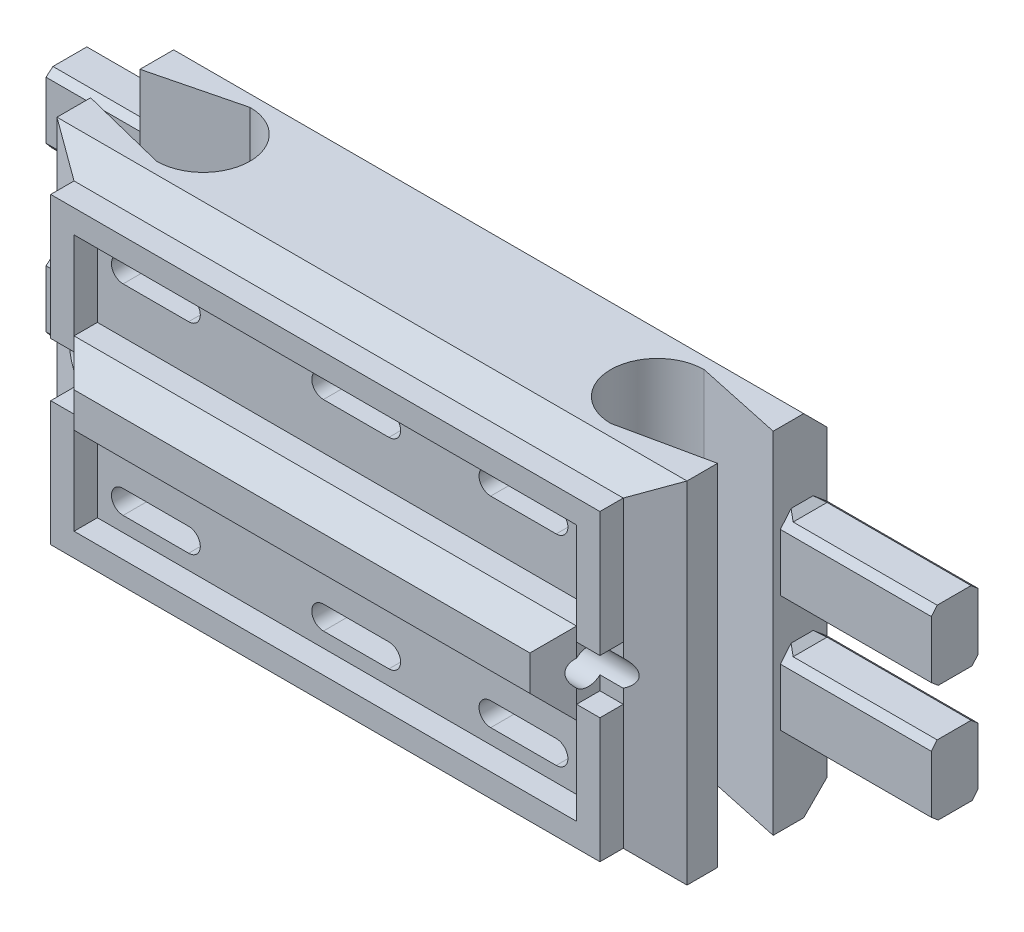
SolidWorks part; units mm, degrees
ref_plane "Front Plane" through (0, 0, 0) normal (0, 0, 1) x (1, 0, 0)
ref_plane "Top Plane" through (0, 0, 0) normal (0, 1, 0) x (1, 0, 0)
ref_plane "Right Plane" through (0, 0, 0) normal (1, 0, 0) x (0, 0, -1)
sketch "Base" plane through (0, 0, 0) normal (0, 0, 1) x (1, 0, 0)
  line L1 (0, 0) -> (27, 0)
  line L2 (0, 0) -> (0, 15)
  line L3 (0, 15) -> (27, 15)
  line L4 (27, 0) -> (27, 15)
  dimension "D1" = 27
  dimension "D2" = 15
extrude "Boss-Extrude1" add sketch "Base" along normal blind 7
chamfer "Chamfer4" distance 1 angle 45 2 edges at (13.5, 15, 7) (13.5, 0, 7)
chamfer "Chamfer5" distance 1 angle 60 2 edges at (0, 7.5, 7) (27, 7.5, 7)
chamfer "Chamfer6" distance 1 angle 45 2 edges at (13.5, 15, 0) (13.5, 0, 0)
sketch "Tendon extrude" plane through (0, 0, 0) normal (0, -1, 0) x (1, 0, 0)
  line L0 (13.5, 6) -> (13.5, -3.9632) construction
  line L1 (27, 6) -> (0, 6) construction
  line L2 (0, 3.5) -> (21.7648, 3.5) construction
  line L3 (0, 6) -> (0, 1) construction
  line L4 (3.77, 3.5) -> (-2.23, 3.5) construction
  line L5 (-2.23, 3) -> (-2.23, 4)
  line L6 (3.77, 5.5) -> (-2.23, 4)
  line L7 (-2.23, 3) -> (3.77, 1.5)
  line L10 (23.23, 3.5) -> (30.23, 3.5) construction
  line L11 (30.23, 3) -> (30.23, 4)
  line L12 (23.23, 5.5) -> (30.23, 4)
  line L13 (30.23, 3) -> (23.23, 1.5)
  circle A0 centre (3.77, 3.5) radius 2
  circle A1 centre (23.23, 3.5) radius 2
  dimension "D1" = 4
  dimension "D2" = 3.77
  dimension "D3" = 1
  dimension "D4" = 6
  dimension "D5" = 1
  dimension "D6" = 7
sketch "Sketch8" plane through (0, 0, 7) normal (0, 0, 1) x (1, 0, 0)
  line L0 (25.2679, 7.5) -> (1.7321, 7.5) construction
  line L1 (25.2679, 1) -> (25.2679, 14) construction
  line L2 (1.7321, 14) -> (1.7321, 1) construction
  line L3 (13.5, 1) -> (13.5, 14) construction
  line L4 (1.7321, 1) -> (25.2679, 1) construction
  line L5 (25.2679, 14) -> (1.7321, 14) construction
  line L6 (2.7321, 5.75) -> (2.7321, 9.25)
  line L7 (24.2679, 9.25) -> (2.7321, 9.25)
  line L8 (24.2679, 9.25) -> (24.2679, 5.75)
  line L9 (24.2679, 5.75) -> (2.7321, 5.75)
  point P17 (2.7321, 7.5)
  point P18 (24.2679, 7.5)
  dimension "D1" = 1.75
  dimension "D2" = 1
  dimension "D3" = 1
extrude "Boss-Extrude5" add sketch "Sketch8" along normal blind 2
sketch "Sketch9" plane through (24.2679, 0, 0) normal (1, 0, 0) x (0, 0, -1)
  line L0 (-9, 7.5) -> (-7, 7.5) construction
  line L1 (-9, 5.75) -> (-9, 9.25) construction
  line L2 (-7, 5.75) -> (-7, 9.25) construction
  circle A0 centre (-7.5, 7.5) radius 0.75
  dimension "D1" = 1.5
  dimension "D2" = 1.5
extrude "Cut-Extrude5" cut sketch "Sketch9" against normal blind 34.5 and the other way blind 4.2544
chamfer "Chamfer9" distance 1 angle 45 4 edges at (2.7321, 7.5, 9) (13.5, 9.25, 9) (24.2679, 7.5, 9) (13.5, 5.75, 9)
sketch "Sketch13" plane through (0, 0, 0) normal (0, 0, -1) x (-1, 0, 0)
  line L0 (0, 7.5) -> (-33.4926, 7.5) construction
  line L1 (0, 14) -> (0, 1) construction
  line L2 (-13.5, 1) -> (-13.5, 15.915) construction
  line L3 (-27, 1) -> (0, 1) construction
  line L4 (-1, 9.25) -> (-8.5, 9.25)
  line L5 (-18.5, 9.25) -> (-18.5, 5.75)
  line L6 (-1, 9.25) -> (-1, 5.75)
  line L7 (-1, 5.75) -> (-8.5, 5.75)
  line L8 (-8.5, 9.25) -> (-8.5, 5.75)
  line L9 (-26, 9.25) -> (-18.5, 9.25)
  line L10 (-26, 5.75) -> (-18.5, 5.75)
  line L11 (-26, 9.25) -> (-26, 5.75)
  point P13 (-8.5, 7.5)
  point P14 (-1, 7.5)
  dimension "D1" = 1.75
  dimension "D2" = 1
  dimension "D3" = 5
extrude "Boss-Extrude6" add sketch "Sketch13" along normal blind 2
chamfer "Chamfer10" distance 1 angle 45 8 edges at (18.5, 7.5, -2) (22.25, 5.75, -2) (26, 7.5, -2) (22.25, 9.25, -2) (4.75, 9.25, -2) (1, 7.5, -2) (4.75, 5.75, -2) (8.5, 7.5, -2)
sketch "Sketch14" plane through (1, 0, 0) normal (-1, 0, 0) x (0, 0, 1)
  line L0 (-1, 7.5) -> (0, 7.5) construction
  line L1 (-1, 9.25) -> (-1, 5.75) construction
  line L2 (0, 5.75) -> (0, 9.25) construction
  line L3 (-2, 6.75) -> (-2, 8.25) construction
  circle A0 centre (-0.5, 7.5) radius 0.75
  dimension "D1" = 1.5
  dimension "D2" = 1.5
extrude "Cut-Extrude6" cut sketch "Sketch14" against normal blind 30 and the other way blind 3
sketch "Sketch15" plane through (0, 0, 0) normal (0, 0, -1) x (-1, 0, 0)
  line L0 (-25, 6.75) -> (-19.5, 6.75) construction
  line L1 (-25, 3.25) -> (-24, 3.25)
  line L2 (-25, 3.25) -> (-25, 6.75)
  line L3 (-25, 6.75) -> (-24, 6.75)
  line L4 (-24, 3.25) -> (-24, 6.75)
  line L5 (-25, 8.25) -> (-25, 6.75) construction
  line L6 (-13.5, 1) -> (-13.5, 14) construction
  line L7 (-27, 1) -> (0, 1) construction
  line L8 (0, 14) -> (-27, 14) construction
  line L9 (-19.5, 8.25) -> (-25, 8.25) construction
  line L10 (-25, 8.25) -> (-24, 8.25)
  line L11 (-25, 8.25) -> (-25, 11.75)
  line L12 (-25, 11.75) -> (-24, 11.75)
  line L13 (-24, 8.25) -> (-24, 11.75)
  line L14 (-2, 3.25) -> (-3, 3.25)
  line L15 (-2, 3.25) -> (-2, 6.75)
  line L16 (-3, 3.25) -> (-3, 6.75)
  line L17 (-2, 6.75) -> (-3, 6.75)
  line L18 (-2, 8.25) -> (-3, 8.25)
  line L19 (-2, 11.75) -> (-3, 11.75)
  line L20 (-3, 8.25) -> (-3, 11.75)
  line L21 (-2, 8.25) -> (-2, 11.75)
  dimension "D1" = 0
  dimension "D2" = 3.5
  dimension "D3" = 1
  dimension "D4" = 0
  dimension "D5" = 0
extrude "Boss-Extrude7" add sketch "Sketch15" along normal blind 2
sketch "Sketch16" plane through (25, 0, 0) normal (1, 0, 0) x (0, 0, -1)
  line L0 (0.6, 5.15) -> (0.6, 4.35) construction
  line L1 (1.2, 5.15) -> (1.2, 4.35)
  line L2 (0, 5.15) -> (0, 4.35)
  line L3 (1, 5.75) -> (0, 5.75) construction
  line L5 (0.6, 9.85) -> (0.6, 10.65) construction
  line L6 (0, 9.85) -> (0, 10.65)
  line L7 (1.2, 9.85) -> (1.2, 10.65)
  line L9 (1, 9.25) -> (0, 9.25) construction
  line L10 (0, 5.75) -> (0, 3.25) construction
  arc A0 (1.2, 5.15) -> (0, 5.15) centre (0.6, 5.15) ccw
  arc A1 (0, 4.35) -> (1.2, 4.35) centre (0.6, 4.35) ccw
  arc A2 (0, 9.85) -> (1.2, 9.85) centre (0.6, 9.85) ccw
  arc A3 (1.2, 10.65) -> (0, 10.65) centre (0.6, 10.65) ccw
  point P2 (0.6, 4.75)
  point P13 (0.6, 10.25)
  point P20 (0.5, 9.25)
  dimension "D1" = 0.8
  dimension "D2" = 0.6
  dimension "D3" = 0.6
  dimension "D4" = 0
  dimension "D5" = 0.6
extrude "Cut-Extrude7" cut sketch "Sketch16" against normal blind 26
chamfer "Chamfer11" distance 0.3 angle 45 8 edges at (2, 5, -2) (3, 5, -2) (3, 10, -2) (2, 10, -2) (25, 10, -2) (24, 10, -2) (25, 5, -2) (24, 5, -2)
chamfer "Chamfer12" distance 0.75 angle 45 4 edges at (24.5, 3.25, -2) (24.5, 11.75, -2) (2.5, 11.75, -2) (2.5, 3.25, -2)
extrude "Cut-Extrude8" cut sketch "Tendon extrude" against normal up to surface (15 mm away)
sketch "Sketch18" plane through (27, 0, 0) normal (1, 0, 0) x (0, 0, -1)
  line L0 (-2.3079, 7.5) -> (-0.25, 7.5) construction
  line L1 (-2.3079, 15) -> (-2.3079, 0) construction
  line L3 (-2, 8.5) -> (0, 8.5)
  line L4 (-2, 8.5) -> (-2, 11.5)
  line L5 (-2, 11.5) -> (0, 11.5)
  line L6 (0, 8.5) -> (0, 11.5)
  line L7 (-2, 6.5) -> (0, 6.5)
  line L8 (0, 6.5) -> (0, 3.5)
  line L9 (-2, 3.5) -> (0, 3.5)
  line L10 (-2, 6.5) -> (-2, 3.5)
  line L11 (0, 8.059) -> (0, 14) construction
  arc A0 (0, 8.059) -> (0, 6.941) centre (0.5, 7.5) ccw construction
  dimension "D1" = 3
  dimension "D2" = 2
  dimension "D3" = 1
extrude "Boss-Extrude8" add sketch "Sketch18" along normal blind 6.47
chamfer "Chamfer13" distance 0.25 angle 50 8 edges at (30.235, 3.5, 2) (30.235, 6.5, 2) (30.235, 8.5, 2) (30.235, 11.5, 2) (30.235, 11.5, 0) (30.235, 8.5, 0) (30.235, 6.5, 0) (30.235, 3.5, 0)
chamfer "Chamfer14" distance 0.25 angle 50 4 edges at (27, 11.5, 1.024) (27, 3.5, 0.976) (27, 6.5, 1.024) (27, 8.5, 0.976)
sketch "Sketch19" plane through (0, 0, 0) normal (-1, 0, 0) x (0, 0, 1)
  line L0 (0.25, 7.5) -> (2.4425, 7.5) construction
  line L1 (2.4425, 15) -> (2.4425, 0) construction
  line L3 (0, 5.5) -> (2, 5.5)
  line L4 (0, 5.5) -> (0, 2.5)
  line L5 (0, 2.5) -> (2, 2.5)
  line L6 (2, 5.5) -> (2, 2.5)
  line L7 (2, 9.5) -> (2, 12.5)
  line L8 (0, 12.5) -> (2, 12.5)
  line L9 (0, 9.5) -> (0, 12.5)
  line L10 (0, 9.5) -> (2, 9.5)
  line L11 (0, 6.941) -> (0, 1) construction
  arc A0 (0, 6.941) -> (0, 8.059) centre (-0.5, 7.5) ccw construction
  dimension "D1" = 2
  dimension "D2" = 3
  dimension "D4" = 2
extrude "Boss-Extrude9" add sketch "Sketch19" along normal blind 4.47
chamfer "Chamfer15" distance 0.25 angle 50 8 edges at (-2.235, 2.5, 2) (-2.235, 5.5, 2) (-2.235, 12.5, 2) (-2.235, 9.5, 2) (-2.235, 2.5, 0) (-2.235, 5.5, 0) (-2.235, 12.5, 0) (-2.235, 9.5, 0)
chamfer "Chamfer16" distance 0.25 angle 50 4 edges at (0, 12.5, 0.976) (0, 9.5, 1.024) (0, 5.5, 0.976) (0, 2.5, 1.024)
sketch "Sketch21" plane through (0, 0, 7) normal (0, 0, 1) x (1, 0, 0)
  line L0 (2.7321, 6.3455) -> (1.7321, 6.3455)
  line L1 (2.7321, 6.941) -> (2.7321, 5.75) construction
  line L2 (1.7321, 6.941) -> (1.7321, 1) construction
  line L3 (1.7321, 6.3455) -> (1.7321, 1)
  line L4 (1.7321, 1) -> (25.2679, 1)
  line L5 (25.2679, 1) -> (25.2679, 6.3455)
  line L6 (25.2679, 1) -> (25.2679, 6.941) construction
  line L7 (25.2679, 6.3455) -> (24.2679, 6.3455)
  line L8 (24.2679, 5.75) -> (24.2679, 6.941) construction
  line L9 (24.2679, 6.3455) -> (24.2679, 2)
  line L10 (24.2679, 2) -> (2.7321, 2)
  line L11 (2.7321, 2) -> (2.7321, 6.3455)
  line L12 (2.7321, 8.6545) -> (1.7321, 8.6545)
  line L13 (2.7321, 9.25) -> (2.7321, 8.059) construction
  line L14 (1.7321, 14) -> (1.7321, 8.059) construction
  line L15 (1.7321, 8.6545) -> (1.7321, 14)
  line L16 (1.7321, 14) -> (25.2679, 14)
  line L17 (25.2679, 14) -> (25.2679, 8.6545)
  line L18 (25.2679, 8.059) -> (25.2679, 14) construction
  line L19 (25.2679, 8.6545) -> (24.2679, 8.6545)
  line L20 (24.2679, 8.059) -> (24.2679, 9.25) construction
  line L21 (24.2679, 8.6545) -> (24.2679, 13)
  line L22 (24.2679, 13) -> (2.7321, 13)
  line L23 (2.7321, 13) -> (2.7321, 8.6545)
  dimension "D1" = 1
  dimension "D2" = 1
extrude "Boss-Extrude10" add sketch "Sketch21" along normal blind 1
sketch "Sketch28" plane through (0, 0, 7) normal (0, 0, 1) x (1, 0, 0)
  line L0 (3.8349, 3.1395) -> (6.6423, 3.1395) construction
  line L1 (3.8349, 3.6395) -> (6.6423, 3.6395)
  line L2 (3.8349, 2.6395) -> (6.6423, 2.6395)
  line L3 (12.419, 3.1395) -> (15.2264, 3.1395) construction
  line L4 (12.419, 3.6395) -> (15.2264, 3.6395)
  line L5 (12.419, 2.6395) -> (15.2264, 2.6395)
  line L6 (19.5873, 3.1395) -> (22.3947, 3.1395) construction
  line L7 (19.5873, 3.6395) -> (22.3947, 3.6395)
  line L8 (19.5873, 2.6395) -> (22.3947, 2.6395)
  line L9 (19.5873, 11.7321) -> (22.3947, 11.7321) construction
  line L10 (19.5873, 12.2321) -> (22.3947, 12.2321)
  line L11 (19.5873, 11.2321) -> (22.3947, 11.2321)
  line L12 (12.419, 11.7321) -> (15.2264, 11.7321) construction
  line L13 (12.419, 12.2321) -> (15.2264, 12.2321)
  line L14 (12.419, 11.2321) -> (15.2264, 11.2321)
  line L15 (3.8349, 11.7321) -> (6.6423, 11.7321) construction
  line L16 (3.8349, 12.2321) -> (6.6423, 12.2321)
  line L17 (3.8349, 11.2321) -> (6.6423, 11.2321)
  arc A0 (3.8349, 3.6395) -> (3.8349, 2.6395) centre (3.8349, 3.1395) ccw
  arc A1 (6.6423, 2.6395) -> (6.6423, 3.6395) centre (6.6423, 3.1395) ccw
  arc A2 (12.419, 3.6395) -> (12.419, 2.6395) centre (12.419, 3.1395) ccw
  arc A3 (15.2264, 2.6395) -> (15.2264, 3.6395) centre (15.2264, 3.1395) ccw
  arc A4 (19.5873, 3.6395) -> (19.5873, 2.6395) centre (19.5873, 3.1395) ccw
  arc A5 (22.3947, 2.6395) -> (22.3947, 3.6395) centre (22.3947, 3.1395) ccw
  arc A6 (19.5873, 12.2321) -> (19.5873, 11.2321) centre (19.5873, 11.7321) ccw
  arc A7 (22.3947, 11.2321) -> (22.3947, 12.2321) centre (22.3947, 11.7321) ccw
  arc A8 (12.419, 12.2321) -> (12.419, 11.2321) centre (12.419, 11.7321) ccw
  arc A9 (15.2264, 11.2321) -> (15.2264, 12.2321) centre (15.2264, 11.7321) ccw
  arc A10 (3.8349, 12.2321) -> (3.8349, 11.2321) centre (3.8349, 11.7321) ccw
  arc A11 (6.6423, 11.2321) -> (6.6423, 12.2321) centre (6.6423, 11.7321) ccw
  point P2 (5.2386, 3.1395)
  point P9 (13.8227, 3.1395)
  point P16 (20.991, 3.1395)
  point P23 (20.991, 11.7321)
  point P30 (13.8227, 11.7321)
  point P37 (5.2386, 11.7321)
extrude "Cut-Extrude9" cut sketch "Sketch28" against normal blind 1
